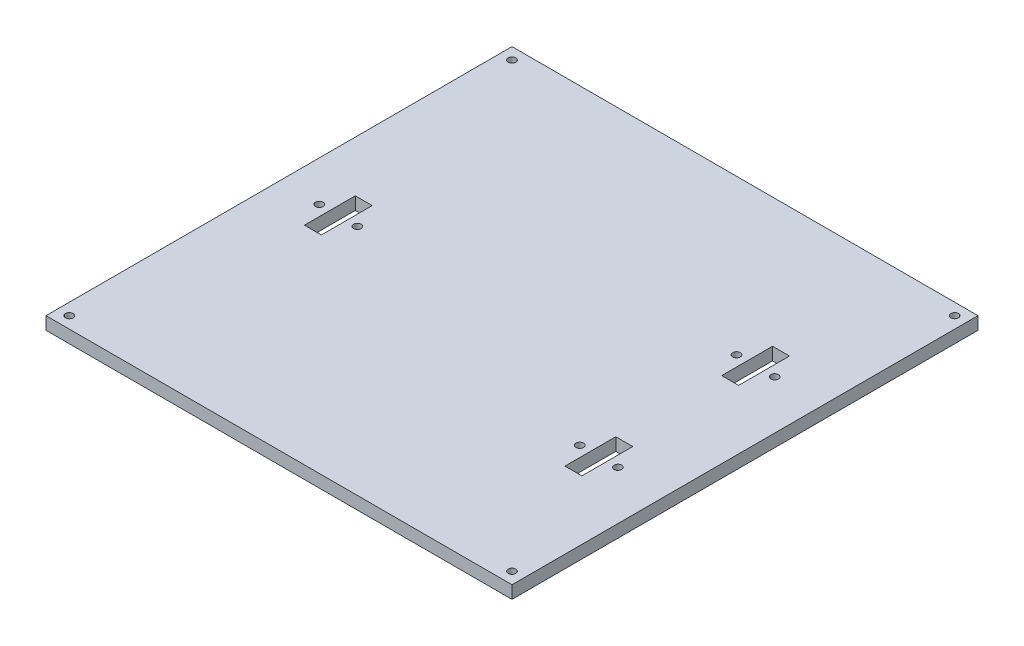
SolidWorks part; units mm, degrees
ref_plane "Front Plane" through (0, 0, 0) normal (0, 0, 1) x (1, 0, 0)
ref_plane "Top Plane" through (0, 0, 0) normal (0, 1, 0) x (1, 0, 0)
ref_plane "Right Plane" through (0, 0, 0) normal (1, 0, 0) x (0, 0, -1)
sketch "Sketch1" plane through (0, 0, 0) normal (0, 1, 0) x (1, 0, 0)
  line L0 (-110, -110) -> (110, 110) construction
  line L1 (-110, 110) -> (110, 110)
  line L2 (-110, 110) -> (-110, -110)
  line L3 (-110, -110) -> (110, -110)
  line L4 (110, 110) -> (110, -110)
  line L5 (-82, 110) -> (-82, -110) construction
  line L6 (78, 25) -> (78, -25) construction
  line L7 (0, 110) -> (0, -110) construction
  line L8 (-78, 0) -> (-73, 0) construction
  line L9 (0, 0) -> (73, 0) construction
  line L10 (-73, 0) -> (0, 0) construction
  line L11 (-86, 12) -> (-78, 12)
  line L12 (-86, 12) -> (-86, -12)
  line L13 (-86, -12) -> (-78, -12)
  line L14 (-78, 12) -> (-78, -12)
  line L15 (73, 0) -> (78, 0) construction
  line L16 (-86, 0) -> (-91, 0) construction
  line L17 (82, 37) -> (87, 37) construction
  line L18 (74, 49) -> (82, 49)
  line L19 (74, 49) -> (74, 25)
  line L20 (74, 25) -> (82, 25)
  line L21 (82, 49) -> (82, 25)
  line L22 (74, -25) -> (82, -25)
  line L23 (74, -25) -> (74, -49)
  line L24 (74, -49) -> (82, -49)
  line L25 (82, -25) -> (82, -49)
  line L26 (74, 37) -> (69, 37) construction
  line L27 (74, -37) -> (69, -37) construction
  line L28 (82, -37) -> (87, -37) construction
  circle A0 centre (-104.5, 104.5) radius 1.8
  circle A1 centre (104.5, 104.5) radius 1.8
  circle A2 centre (104.5, -104.5) radius 1.8
  circle A3 centre (-104.5, -104.5) radius 1.8
  circle A4 centre (-73, 0) radius 1.8
  circle A5 centre (-91, 0) radius 1.8
  circle A6 centre (87, 37) radius 1.8
  circle A7 centre (69, 37) radius 1.8
  circle A8 centre (87, -37) radius 1.8
  circle A9 centre (69, -37) radius 1.8
  point P26 (-82, 12)
  dimension "D3" = 3.6
  dimension "D4" = 5.5
  dimension "D5" = 5.5
  dimension "D9" = 160
  dimension "D10" = 209
  dimension "D1" = 220
  dimension "D2" = 50
  dimension "D6" = 24
  dimension "D7" = 8
  dimension "D8" = 5
extrude "Boss-Extrude1" add sketch "Sketch1" along normal mid plane 6
